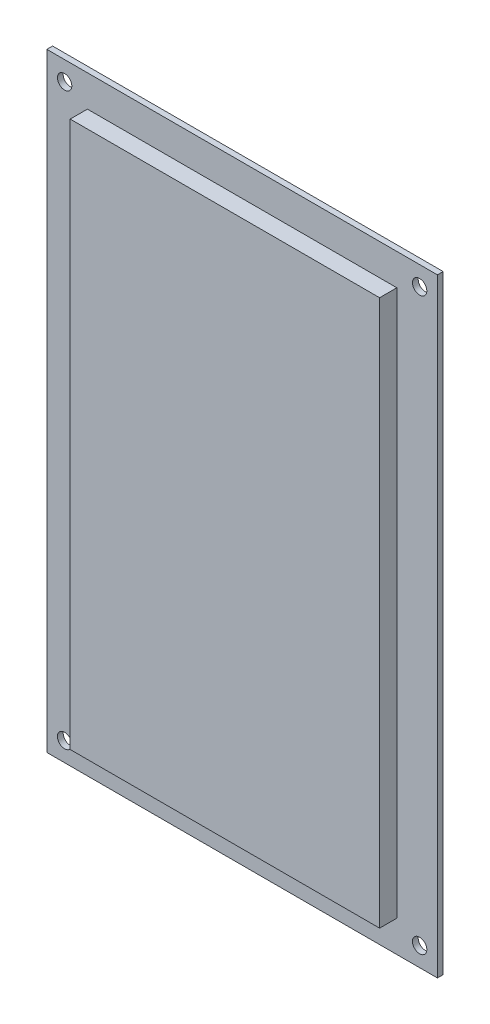
SolidWorks part; units mm, degrees
ref_plane "Front Plane" through (0, 0, 0) normal (0, 0, 1) x (1, 0, 0)
ref_plane "Top Plane" through (0, 0, 0) normal (0, 1, 0) x (1, 0, 0)
ref_plane "Right Plane" through (0, 0, 0) normal (1, 0, 0) x (0, 0, -1)
sketch "Sketch2" plane through (0, 0, 0) normal (0, 0, 1) x (1, 0, 0)
  line L0 (-20.017, 37.185) -> (33.843, 37.185) construction
  line L1 (-20.017, 43.585) -> (33.843, 43.585)
  line L2 (-20.017, 43.585) -> (-20.017, -51.455)
  line L3 (-20.017, -51.455) -> (33.843, -51.455)
  line L4 (33.843, 43.585) -> (33.843, -51.455)
  line L5 (-20.017, -41.055) -> (33.843, -41.055) construction
  line L6 (6.913, 43.585) -> (6.913, -51.455) construction
  dimension "D1" = 95.04
  dimension "D2" = 53.86
  dimension "D3" = 6.4
  dimension "D4" = 10.4
extrude "Boss-Extrude1" add sketch "Sketch2" along normal blind 3
sketch "Sketch3" plane through (0, 0, 0) normal (0, 0, -1) x (-1, 0, 0)
  line L0 (-6.913, -51.455) -> (-6.913, 43.585) construction
  line L1 (20.017, -51.455) -> (-33.843, -51.455) construction
  line L2 (-33.843, 43.585) -> (20.017, 43.585) construction
  line L3 (-33.843, -3.935) -> (20.017, -3.935) construction
  line L4 (-33.843, -51.455) -> (-33.843, 43.585) construction
  line L5 (20.017, 43.585) -> (20.017, -51.455) construction
  line L6 (-49.2074, -53.585) -> (-49.2074, -51.455) construction
  line L7 (-40.913, 49.065) -> (27.087, 49.065)
  line L8 (-40.913, 49.065) -> (-40.913, -56.935)
  line L9 (-40.913, -56.935) -> (27.087, -56.935)
  line L10 (27.087, 49.065) -> (27.087, -56.935)
  line L11 (-40.913, 49.065) -> (27.087, -56.935) construction
  line L12 (-40.913, -56.935) -> (27.087, 49.065) construction
  line L13 (-55.5095, 45.715) -> (-55.5095, 43.585) construction
  line L14 (20.017, 43.585) -> (-33.843, 43.585) construction
  line L15 (-33.843, -51.455) -> (20.017, -51.455) construction
  circle A0 centre (23.987, 45.715) radius 1.25
  circle A1 centre (23.987, -53.585) radius 1.25
  circle A2 centre (-37.813, 45.715) radius 1.25
  circle A3 centre (-37.813, -53.585) radius 1.25
  point P12 (-6.913, -3.935)
  dimension "D1" = 2.5
  dimension "D2" = 106
  dimension "D3" = 68
  dimension "D4" = 61.8
  dimension "D5" = 99.3
extrude "Boss-Extrude2" add sketch "Sketch3" along normal blind 1
